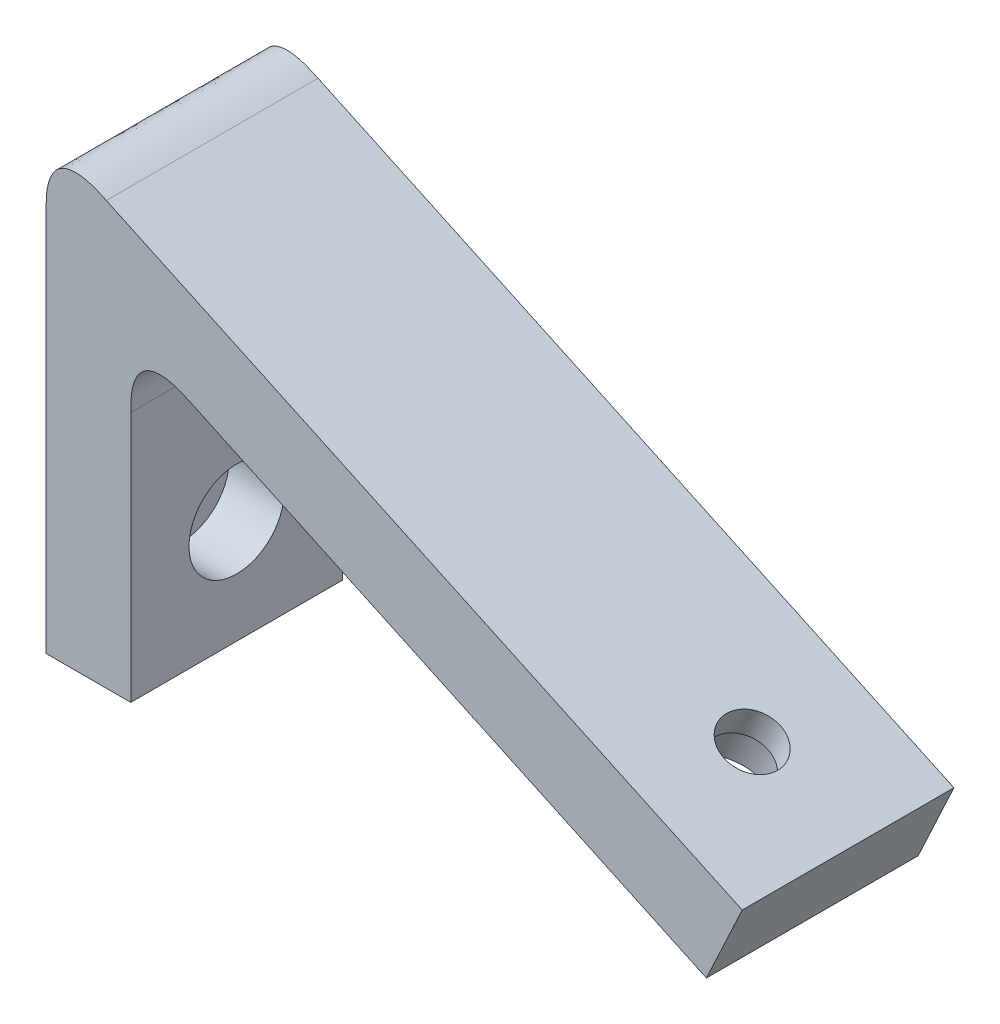
SolidWorks part; units mm, degrees
ref_plane "Front Plane" through (0, 0, 0) normal (0, 0, 1) x (1, 0, 0)
ref_plane "Top Plane" through (0, 0, 0) normal (0, 1, 0) x (1, 0, 0)
ref_plane "Right Plane" through (0, 0, 0) normal (1, 0, 0) x (0, 0, -1)
sketch "Sketch1" plane through (0, 0, 0) normal (0, 0, 1) x (1, 0, 0)
  line L0 (0, 0) -> (0, 54.048)
  line L1 (0, 54.048) -> (83.5145, 15.1046)
  line L2 (83.5145, 15.1046) -> (79.2207, 5.8965)
  line L3 (79.2207, 5.8965) -> (10.16, 38.1)
  line L4 (10.16, 38.1) -> (10.16, 0)
  line L5 (10.16, 0) -> (0, 0)
  dimension "D1" = 38.1
  dimension "D2" = 76.2
  dimension "D3" = 65
  dimension "D4" = 10.16
  dimension "D5" = 10.16
extrude "Boss-Extrude1" add sketch "Sketch1" along normal blind 25.4 contours L5 L4 L3 L2 L1 L0 region at (0.9948, 27.024, 0)
sketch "Sketch2" plane through (0, 0, 0) normal (-1, 0, 0) x (0, 0, 1)
  line L0 (0, 12.7) -> (25.4, 12.7) construction
  line L1 (0, 0) -> (0, 54.048) construction
  line L2 (25.4, 0) -> (25.4, 54.048) construction
  line L3 (25.4, 0) -> (0, 0) construction
  point P6 (12.7, 12.7)
  dimension "D1" = 12.7
sketch "Sketch3" plane through (20.7016, 44.3947, 0) normal (0.4226, 0.9063, 0) x (0.9063, -0.4226, 0)
  line L0 (56.6063, 0) -> (56.6063, -25.4) construction
  line L1 (-22.8417, 0) -> (69.3063, 0) construction
  line L2 (-22.8417, -25.4) -> (69.3063, -25.4) construction
  line L3 (69.3063, -25.4) -> (69.3063, 0) construction
  point P6 (56.6063, -12.7)
  dimension "D1" = 12.7
hole_wizard "1/4 Clearance Hole1" positions "Sketch4" profile "Sketch5" hole size "1/4" standard "ANSI Inch"
sketch "Sketch4" plane through (0, 0, 0) normal (-1, 0, 0) x (0, 0, 1)
  point P0 (12.7, 12.7)
sketch "Sketch5" plane through (0, 12.7, 12.7) normal (0, 1, 0) x (0, 0, 1)
  line L0 (0, 0) -> (0, 12.1898)
  line L1 (0, 12.1898) -> (3.3782, 10.16)
  line L2 (3.3782, 10.16) -> (3.3782, 0)
  line L5 (3.3782, 0) -> (0, 0)
  line L10 (0, 12.1898) -> (-3.3782, 10.16) construction
  line L11 (0, -6.35) -> (0, 107.95) construction
  dimension "Hole Dia." = 6.7564
  dimension "Hole Depth" = 10.16
  dimension "Drill Angle" = 118
hole_wizard "1/4 Clearance Hole2" positions "Sketch6" profile "Sketch7" hole size "1/4" standard "ANSI Inch"
sketch "Sketch6" plane through (20.7016, 44.3947, 0) normal (0.4226, 0.9063, 0) x (0.9063, -0.4226, 0)
  point P0 (56.6063, -12.7)
sketch "Sketch7" plane through (72.0043, 20.4718, 12.7) normal (0, 0, 1) x (-0.9063, 0.4226, 0)
  line L0 (0, 0) -> (0, 12.1898)
  line L1 (0, 12.1898) -> (3.3782, 10.16)
  line L2 (3.3782, 10.16) -> (3.3782, 0)
  line L5 (3.3782, 0) -> (0, 0)
  line L10 (0, 12.1898) -> (-3.3782, 10.16) construction
  line L11 (0, -6.35) -> (0, 107.95) construction
  dimension "Hole Dia." = 6.7564
  dimension "Hole Depth" = 10.16
  dimension "Drill Angle" = 118
fillet "Fillet1" radius 5.08 2 edges at (10.16, 38.1, 12.7) (0, 54.048, 12.7) curvature continuous yes
sketch "Sketch8" plane through (16.4078, 35.1866, 0) normal (-0.4226, -0.9063, 0) x (0.9063, -0.4226, 0)
  circle A0 centre (56.6063, 12.7) radius 5.715
  dimension "D1" = 11.43
extrude "Cut-Extrude1" cut sketch "Sketch8" against normal blind 6.604
sketch "Sketch9" plane through (10.16, 0, 0) normal (1, 0, 0) x (0, 0, -1)
  line L0 (0, 12.7) -> (-25.4, 12.7) construction
  circle A0 centre (-12.7, 12.7) radius 5.715
  dimension "D1" = 11.43
extrude "Cut-Extrude2" cut sketch "Sketch9" against normal blind 6.604
